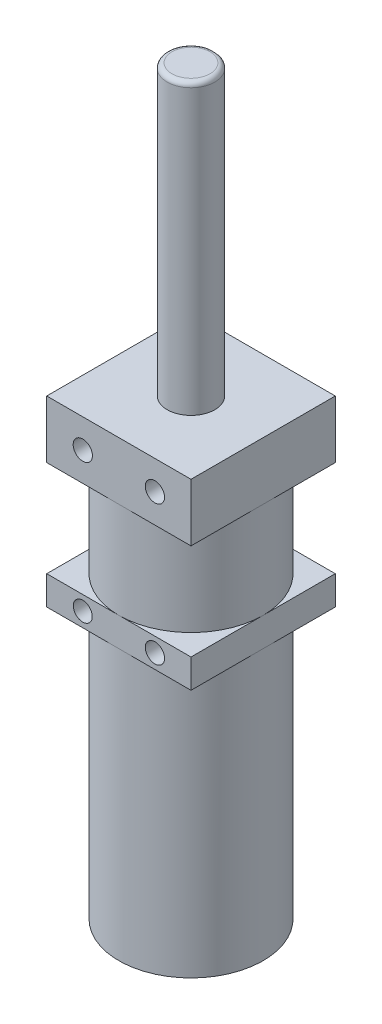
SolidWorks part; units mm, degrees
ref_plane "Front Plane" through (0, 0, 0) normal (0, 0, 1) x (1, 0, 0)
ref_plane "Top Plane" through (0, 0, 0) normal (0, 1, 0) x (1, 0, 0)
ref_plane "Right Plane" through (0, 0, 0) normal (1, 0, 0) x (0, 0, -1)
sketch "Sketch1" plane through (0, 0, 0) normal (0, 1, 0) x (1, 0, 0)
  line L1 (19.05, -19.05) -> (-19.05, -19.05)
  line L2 (19.05, -19.05) -> (19.05, 19.05)
  line L3 (19.05, 19.05) -> (-19.05, 19.05)
  line L4 (-19.05, -19.05) -> (-19.05, 19.05)
  line L5 (19.05, -19.05) -> (-19.05, 19.05) construction
  line L6 (19.05, 19.05) -> (-19.05, -19.05) construction
  point P0 (0, 0)
  dimension "D1" = 38.1
  dimension "D2" = 38.1
extrude "Boss-Extrude1" add sketch "Sketch1" along normal blind 7.62
sketch "Sketch2" plane through (0, 7.62, 0) normal (0, 1, 0) x (1, 0, 0)
  circle A0 centre (0, 0) radius 19.05
extrude "Boss-Extrude2" add sketch "Sketch2" along normal blind 25.4
sketch "Sketch3" plane through (0, 33.02, 0) normal (0, 1, 0) x (1, 0, 0)
  line L1 (19.05, 19.05) -> (-19.05, 19.05)
  line L2 (19.05, 19.05) -> (19.05, -19.05)
  line L3 (19.05, -19.05) -> (-19.05, -19.05)
  line L4 (-19.05, 19.05) -> (-19.05, -19.05)
  line L5 (19.05, 19.05) -> (-19.05, -19.05) construction
  line L6 (19.05, -19.05) -> (-19.05, 19.05) construction
  point P0 (0, 0)
  dimension "D1" = 38.1
  dimension "D2" = 38.1
extrude "Boss-Extrude3" add sketch "Sketch3" along normal blind 15.24
sketch "Sketch4" plane through (0, 48.26, 0) normal (0, 1, 0) x (1, 0, 0)
  circle A0 centre (0, 0) radius 6.2965
  dimension "D1" = 12.5929
extrude "Boss-Extrude4" add sketch "Sketch4" along normal blind 76.2
sketch "Sketch5" plane through (0, 124.46, 0) normal (0, 1, 0) x (1, 0, 0)
  line L1 (-1.5875, 7.175) -> (1.5875, 7.175)
  line L2 (-1.5875, 7.175) -> (-1.5875, 5.588)
  line L3 (-1.5875, 5.588) -> (1.5875, 5.588)
  line L4 (1.5875, 7.175) -> (1.5875, 5.588)
  dimension "D1" = 5.588
  dimension "D2" = 3.175
  dimension "D3" = 1.5875
extrude "Cut-Extrude1" cut sketch "Sketch5" against normal blind 73.66
fillet "Fillet1" radius 1.27 1 edges at (0, 124.46, 6.2965)
sketch "Sketch6" plane through (0, 0, -19.05) normal (0, 0, -1) x (-1, 0, 0)
  line L0 (-19.05, 7.62) -> (-19.05, 0) construction
  line L1 (19.05, 7.62) -> (19.05, 0) construction
  line L2 (-19.05, 0) -> (19.05, 0) construction
  line L3 (-19.05, 48.26) -> (-19.05, 33.02) construction
  line L4 (19.05, 48.26) -> (19.05, 33.02) construction
  line L5 (-19.05, 48.26) -> (19.05, 48.26) construction
  circle A0 centre (-9.525, 3.81) radius 2.54
  circle A1 centre (-9.525, 40.64) radius 2.54
  circle A2 centre (9.525, 40.64) radius 2.54
  circle A3 centre (9.525, 3.81) radius 2.5
  dimension "D1" = 5
  dimension "D2" = 5.08
  dimension "D3" = 5.08
  dimension "D4" = 5.08
  dimension "D5" = 9.525
  dimension "D6" = 9.525
  dimension "D7" = 3.81
  dimension "D8" = 3.81
  dimension "D10" = 9.525
  dimension "D11" = 7.62
  dimension "D12" = 7.62
  dimension "D9" = 9.525
extrude "Cut-Extrude2" cut sketch "Sketch6" against normal blind 7.62
mirror "Mirror1" about plane through (0, 0, 0) normal (0, 0, 1) of "Cut-Extrude2"
sketch "Sketch7" plane through (0, 0, 0) normal (0, -1, 0) x (1, 0, 0)
  circle A0 centre (0, 0) radius 19.05
  dimension "D1" = 38.1
extrude "Boss-Extrude5" add sketch "Sketch7" along normal blind 71.374
